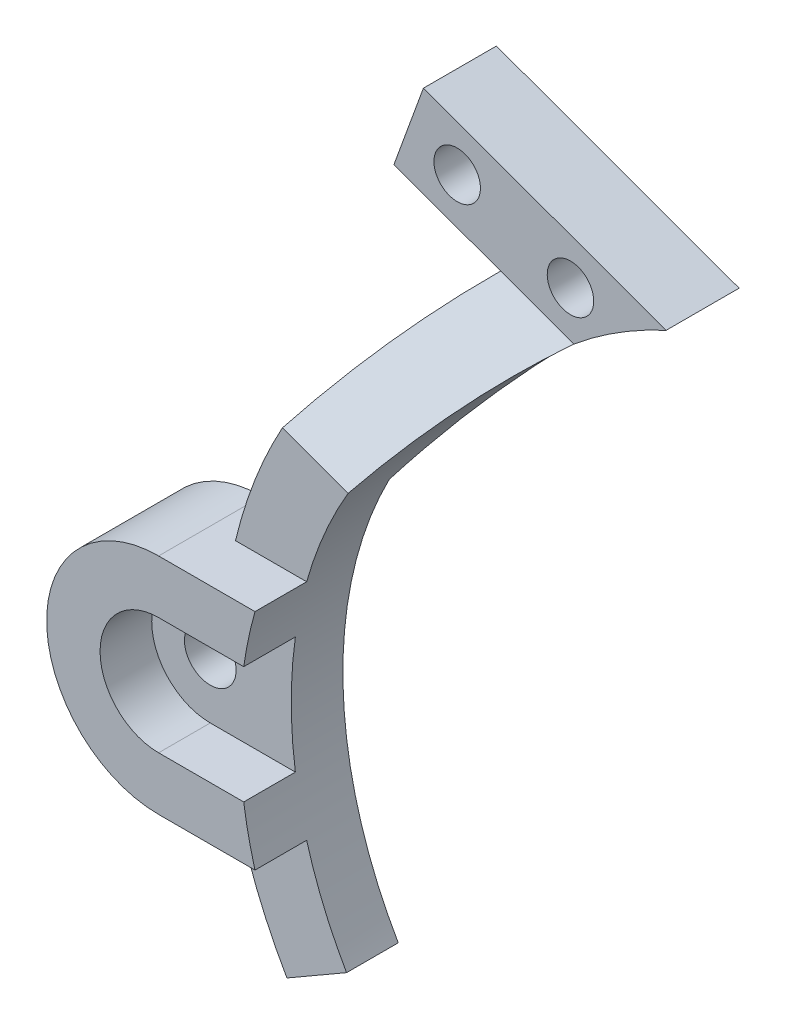
SolidWorks part; units mm, degrees
ref_plane "Plano frontal" through (0, 0, 0) normal (0, 0, 1) x (1, 0, 0)
ref_plane "Plano superior" through (0, 0, 0) normal (0, 1, 0) x (1, 0, 0)
ref_plane "Plano direito" through (0, 0, 0) normal (1, 0, 0) x (0, 0, -1)
sketch "Esboço1" plane through (0, 0, 0) normal (0, 0, 1) x (1, 0, 0)
  line L0 (0, 3.4) -> (4.9421, 3.4)
  line L1 (0, 6.5) -> (5.597, 6.5)
  line L2 (4.9421, -3.4) -> (0, -3.4)
  line L3 (0, -6.5) -> (5.597, -6.5)
  line L4 (18.7132, 21.8235) -> (4.6178, 26.9538)
  line L5 (4.6178, 26.9538) -> (2.9077, 22.2553)
  line L6 (2.9077, 22.2553) -> (9.1041, 20)
  line L7 (1.5, 0) -> (4.7, 0) construction
  line L8 (4.4513, -14) -> (7.9154, -12)
  line L9 (6.5818, 23.5785) -> (13.1597, 21.1843) construction
  line L10 (10.7258, 24.7306) -> (9.8707, 22.3814) construction
  circle A0 centre (0, 0) radius 1.5
  arc A1 (0, 3.4) -> (0, -3.4) centre (0, 0) ccw
  arc A2 (18.7132, 21.8235) -> (7.9154, -12) centre (28.7, 0) ccw
  arc A3 (0, 6.5) -> (0, -6.5) centre (0, 0) ccw
  arc A4 (9.1041, 20) -> (1.4649, 6.5) centre (28.7, 0) ccw
  arc A5 (18.7132, 21.8235) -> (5.597, -6.5) centre (28.7, 0) ccw construction
  arc A6 (17.0487, 25.4607) -> (1.7465, -7.5833) centre (28.7, 0) ccw construction
  arc A7 (4.4513, -14) -> (1.4649, -6.5) centre (28.7, 0) cw
  circle A8 centre (13.1597, 21.1843) radius 1.35
  circle A9 centre (6.5818, 23.5785) radius 1.35
  point P31 (3.7627, 24.6045)
  dimension "D1" = 6.8
  dimension "D2" = 24
  dimension "D3" = 6.5
  dimension "D4" = 3
  dimension "D5" = 20
  dimension "D11" = 4
  dimension "D13" = 7
  dimension "D14" = 2.7
  dimension "D7" = 3.2
  dimension "D8" = 5
  dimension "D9" = 15
  dimension "D10" = 20
  dimension "D12" = 30
  dimension "D15" = 3
  dimension "D6" = 4
extrude "Ressalto-extrusão1" add sketch "Esboço1" along normal blind 15 contours L1 A3 L3 A2 L2 A1 L0 region at (-3.5776, 0, 0)
extrude "Ressalto-extrusão2" add sketch "Esboço1<3>" along normal blind 12 contours A2 L0 A1 L2 A0 region at (2.471, 3.2924, 0)
sketch "Esboço1<3>" plane through (0, 0, 0) normal (0, 0, 1) x (1, 0, 0) same geometry as "Esboço1"
extrude "Ressalto-extrusão3" add sketch "Esboço1<4>" along normal blind 12 contours L6 A4 L1 A2 L4 L5 | A7 L8 A2 L3 region at (8.2124, 17.5843, 0) region at (4.6114, -9.8357, 0)
sketch "Esboço1<4>" plane through (0, 0, 0) normal (0, 0, 1) x (1, 0, 0) same geometry as "Esboço1"
sketch "Esboço2" plane through (-4.5852, 1.6689, 0) normal (-0.9397, 0.342, 0) x (0, 0, 1)
  line L0 (0, -11.6333) -> (9, -11.6333)
  line L1 (12, -11.6333) -> (0, -11.6333) construction
  line L2 (9, -11.6333) -> (9, 12.9076)
  line L3 (9, 12.9076) -> (0, 21.9076)
  line L4 (4.2426, 26.9076) -> (4.2426, 21.9076)
  line L5 (12, 26.9076) -> (0, 26.9076) construction
  line L6 (12, 21.9076) -> (0, 21.9076) construction
  line L7 (4.2426, 21.9076) -> (12, 14.1503)
  line L8 (12, 6.609) -> (12, 21.9076) construction
  line L9 (4.2426, 26.9076) -> (12, 26.9076)
  line L10 (12, 26.9076) -> (12, 14.1503)
  line L11 (0, 21.9076) -> (0, -11.6333)
  dimension "D1" = 3
  dimension "D2" = 45
  dimension "D3" = 3
extrude "Corte-extrusão1" cut sketch "Esboço2" against normal through all both and the other way through all
